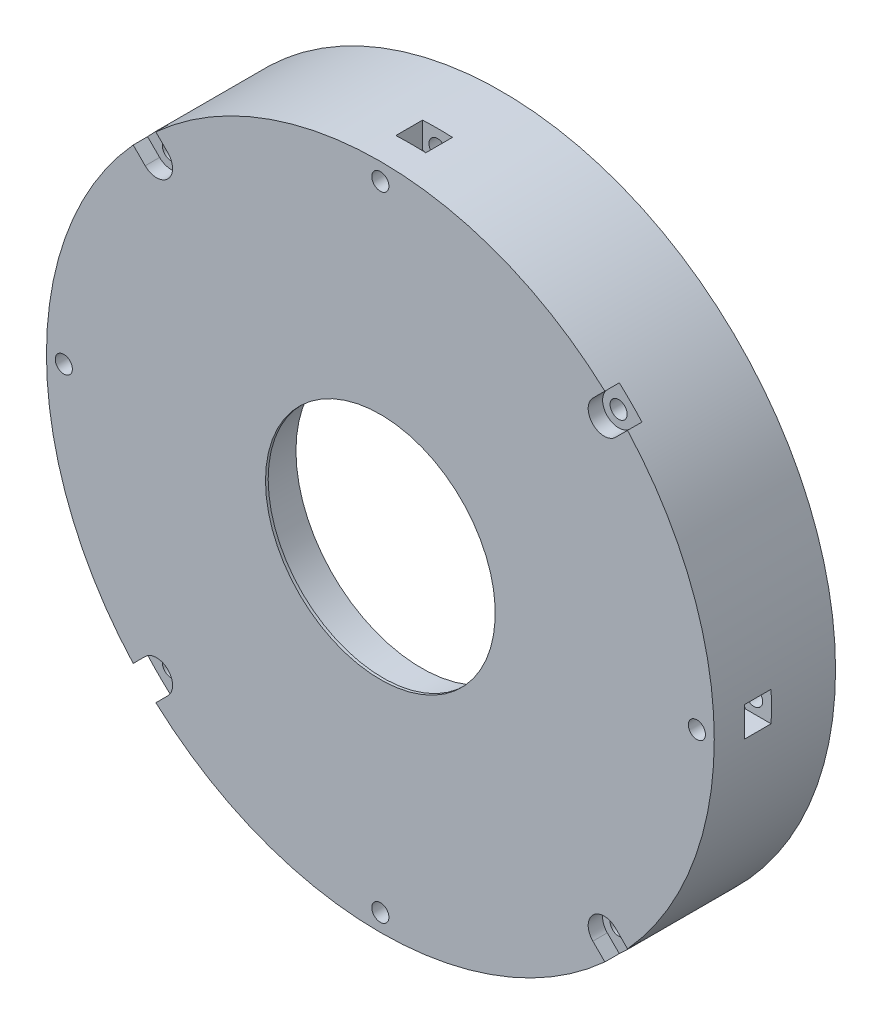
SolidWorks part; units mm, degrees
ref_plane "Front Plane" through (0, 0, 0) normal (0, 0, 1) x (1, 0, 0)
ref_plane "Top Plane" through (0, 0, 0) normal (0, 1, 0) x (1, 0, 0)
ref_plane "Right Plane" through (0, 0, 0) normal (1, 0, 0) x (0, 0, -1)
sketch "Sketch1" plane through (0, 0, 0) normal (1, 0, 0) x (0, 0, -1)
  line L0 (-8.0883, 62.5) -> (-30.7883, 62.5)
  line L1 (-30.7883, 62.5) -> (-30.7883, 21.5)
  line L2 (-30.7883, 21.5) -> (-30.2883, 21.5)
  line L3 (-30.2883, 21.5) -> (-30.2883, 23.5)
  line L4 (-30.2883, 23.5) -> (-23.0883, 23.5)
  line L5 (-8.0883, 50.75) -> (-8.0883, 62.5)
  line L6 (0, 0) -> (-105.8366, 0) construction
  line L7 (-23.0883, 23.5) -> (-23.0883, 50.75)
  line L8 (-23.0883, 50.75) -> (-8.0883, 50.75)
  line L9 (-8.0883, 52.5) -> (-30.7883, 52.5) construction
  line L12 (-26.7883, 23.5) -> (-26.7883, -23.5) construction
  line L13 (-26.7883, 23.5) -> (-26.7883, -23.5) construction
  line L14 (-26.7883, 17.5) -> (-26.7883, -17.5) construction
  line L15 (-26.7883, 17.5) -> (-26.7883, -17.5) construction
  line L16 (-23.2883, 0) -> (-30.2883, 0) construction
  line L17 (-23.2883, 0) -> (-30.2883, 0) construction
  dimension "D1" = 125
  dimension "D2" = 0.5
  dimension "D4" = 105
  dimension "D5" = 101.5
  dimension "D3" = 15
  dimension "D8" = 0.2
revolve "Revolve1" add sketch "Sketch1" angle 360 about L6
sketch "Sketch2" plane through (0, 0, 8.0883) normal (0, 0, -1) x (-1, 0, 0)
  line L3 (0, 0) -> (0, 52.5) construction
  line L4 (0, 52.5) -> (-16.8732, 46.3587)
  line L5 (-16.8732, 46.3587) -> (0, 0) construction
  circle A0 centre (0, 0) radius 52.5 construction
  circle A1 centre (0, 0) radius 54.6875 construction
  circle A2 centre (0, 0) radius 50.75 construction
  circle A3 centre (0, 0) radius 49.3339 construction
  arc A4 (0.7353, 49.3284) -> (-16.8732, 46.3587) centre (0, 0) ccw
  dimension "D1" = 105
  dimension "D2" = 101.5
  dimension "D3" = 109.375
  dimension "D4" = 20
sketch "Sketch4" plane through (0, 0, 8.0883) normal (0, 0, -1) x (-1, 0, 0)
  line L0 (0, 52.5) -> (-16.8732, 46.3587) construction
  line L1 (0, 52.5) -> (-16.8732, 46.3587)
  line L2 (-24.9846, 42.5394) -> (-1.76, 56.1799) construction
  line L3 (-32.2709, 37.3151) -> (-5.1077, 60.8064) construction
  line L4 (-38.4914, 30.8584) -> (-10.4125, 65.8827) construction
  line L5 (-43.4406, 23.3826) -> (-17.9089, 70.8158) construction
  line L6 (-46.9551, 15.1345) -> (-27.6753, 74.9503) construction
  line L7 (-8.2044, 48.6469) -> (0.6486, 50.1399) construction
  arc A0 (-16.8732, 46.3587) -> (-24.9846, 42.5394) centre (0, 0) ccw
  arc A1 (-8.2044, 48.6469) -> (-16.8732, 46.3587) centre (0, 0) ccw
  circle A2 centre (0, 0) radius 49.3339 construction
  arc A3 (-8.2044, 48.6469) -> (0.7353, 49.3284) centre (0, 0) cw
  arc A4 (0.7353, 49.3284) -> (-16.8732, 46.3587) centre (0, 0) ccw construction
  arc A5 (-24.9846, 42.5394) -> (-32.2709, 37.3151) centre (0, 0) ccw
  arc A6 (-32.2709, 37.3151) -> (-38.4914, 30.8584) centre (0, 0) ccw
  arc A7 (-38.4914, 30.8584) -> (-43.4406, 23.3826) centre (0, 0) ccw
  arc A8 (-43.4406, 23.3826) -> (-46.9551, 15.1345) centre (0, 0) ccw
  dimension "D1" = 17.9561
  dimension "D3" = 26.9341
  dimension "D4" = 35.9121
  dimension "D5" = 44.8901
  dimension "D6" = 53.8682
  dimension "D7" = 62.8462
  dimension "D9" = 8.978
  dimension "D2" = 8.978
  dimension "D8" = 8.978
sketch "Sketch5" plane through (0, 0, 8.0883) normal (0, 0, -1) x (-1, 0, 0)
  line L0 (0, 0) -> (-1.9064, 72.801) construction
  line L2 (0, 0) -> (0, 52.5) construction
  arc A0 (-1.9168, 54.6539) -> (-0.9462, 54.6793) centre (0, 0) cw
  circle A2 centre (0, 0) radius 54.6875 construction
  arc A4 (0.5323, 50.7472) -> (-3.1874, 50.6498) centre (0, 0) ccw
  circle A5 centre (0, 0) radius 50.75 construction
  spline S0 degree 3 poles (-27.6753, 74.9503) (-21.4797, 72.9452) (-13.2709, 68.8552) (-5.3211, 61.3461) (-1.9111, 56.7226) (0.0065, 52.7985) (0.676, 50.4181) (0.7353, 49.3284) knots 0 0 0 0 0.489788 0.67346 0.816315 0.918356 1 1 1 1
  spline S1 degree 3 poles (23.7148, 76.296) (17.6326, 73.9694) (9.6491, 69.4554) (2.1032, 61.5405) (-1.0602, 56.7449) (-2.7697, 52.7258) (-3.3138, 50.3136) (-3.3159, 49.2223) knots 0 0 0 0 0.489788 0.67346 0.816315 0.918356 1 1 1 1
  circle M2 centre (0, 0) radius 50.75
  dimension "D1" = 1.5
extrude "Cut-Extrude1" cut sketch "Sketch5" against normal up to surface (15 mm away) contours L0 A4 S0 A0 | L0 A0 S1 M2 region at (2.0632, 52.3141, 8.0883) region at (0.6775, 52.3504, 8.0883) up to face at (-50.75, 0, 23.0883)
pattern_circular "CirPattern1" count 60 over 360 about axis through (0, 0, 0) along (0, 0, -1) of "Cut-Extrude1" reverse direction yes
sketch "Sketch6" plane through (0, 0, 30.7883) normal (0, 0, 1) x (1, 0, 0)
  line L0 (0, 0) -> (0, 45) construction
  circle A0 centre (0, 45) radius 2.5
  circle A1 centre (45, 0) radius 2.5
  circle A2 centre (0, -45) radius 2.5
  circle A3 centre (-45, 0) radius 2.5
  point P13 (0, 0)
  dimension "D1" = 5
  dimension "D2" = 45
  dimension "D3" = 4
extrude "Cut-Extrude2" [suppressed] cut sketch "Sketch6" against normal blind 6
sketch "Sketch7" plane through (0, 0, 23.0883) normal (0, 0, -1) x (-1, 0, 0)
  circle A0 centre (0, 0) radius 27
  circle A1 centre (0, 0) radius 36
  dimension "D1" = 54
  dimension "D2" = 72
extrude "Cut-Extrude3" cut sketch "Sketch7" against normal blind 4
sketch "Sketch8" plane through (0, 0, 8.0883) normal (0, 0, -1) x (-1, 0, 0)
  line L0 (-2.8, 60.8666) -> (-2.8, 62.4372)
  line L1 (0, 56.0168) -> (2.8, 57.6334)
  line L2 (2.8, 57.6334) -> (2.8, 60.8666)
  line L3 (2.8, 60.8666) -> (0, 62.4832) construction
  line L4 (0, 62.4832) -> (-2.8, 60.8666) construction
  line L5 (-2.8, 60.8666) -> (-2.8, 57.6334)
  line L6 (-2.8, 57.6334) -> (0, 56.0168)
  line L7 (2.8, 60.8666) -> (2.8, 62.4372)
  line L8 (60.8666, 2.8) -> (62.4372, 2.8)
  line L9 (56.0168, 0) -> (57.6334, -2.8)
  line L10 (57.6334, -2.8) -> (60.8666, -2.8)
  line L11 (60.8666, 2.8) -> (57.6334, 2.8)
  line L12 (57.6334, 2.8) -> (56.0168, 0)
  line L13 (60.8666, -2.8) -> (62.4372, -2.8)
  line L14 (60.8666, -2.8) -> (62.4832, 0) construction
  line L15 (62.4832, 0) -> (60.8666, 2.8) construction
  line L16 (2.8, -60.8666) -> (2.8, -62.4372)
  line L17 (0, -56.0168) -> (-2.8, -57.6334)
  line L18 (-2.8, -57.6334) -> (-2.8, -60.8666)
  line L19 (2.8, -60.8666) -> (2.8, -57.6334)
  line L20 (2.8, -57.6334) -> (0, -56.0168)
  line L21 (-2.8, -60.8666) -> (-2.8, -62.4372)
  line L22 (-2.8, -60.8666) -> (0, -62.4832) construction
  line L23 (0, -62.4832) -> (2.8, -60.8666) construction
  line L24 (-60.8666, -2.8) -> (-62.4372, -2.8)
  line L25 (-56.0168, 0) -> (-57.6334, 2.8)
  line L26 (-57.6334, 2.8) -> (-60.8666, 2.8)
  line L27 (-60.8666, -2.8) -> (-57.6334, -2.8)
  line L28 (-57.6334, -2.8) -> (-56.0168, 0)
  line L29 (-60.8666, 2.8) -> (-62.4372, 2.8)
  line L30 (-60.8666, 2.8) -> (-62.4832, 0) construction
  line L31 (-62.4832, 0) -> (-60.8666, -2.8) construction
  line L32 (0, 59.25) -> (0, 0) construction
  line L33 (0, 0) -> (41.8961, 41.8961) construction
  line L34 (44.0174, 39.7748) -> (46.2646, 42.0219)
  line L35 (39.7748, 44.0174) -> (42.0219, 46.2646)
  line L36 (39.7748, -44.0174) -> (42.0219, -46.2646)
  line L37 (44.0174, -39.7748) -> (46.2646, -42.0219)
  line L38 (-44.0174, -39.7748) -> (-46.2646, -42.0219)
  line L39 (-39.7748, -44.0174) -> (-42.0219, -46.2646)
  line L40 (-39.7748, 44.0174) -> (-42.0219, 46.2646)
  line L41 (-44.0174, 39.7748) -> (-46.2646, 42.0219)
  line L42 (0, 59.25) -> (0, 62.5) construction
  circle A0 centre (0, 59.25) radius 1.6
  circle A1 centre (0, 59.25) radius 2.8 construction
  circle A2 centre (0, 0) radius 62.5 construction
  arc A3 (2.8, 62.4372) -> (-2.8, 62.4372) centre (0, 0) ccw
  circle A4 centre (59.25, 0) radius 1.6
  arc A5 (62.4372, -2.8) -> (62.4372, 2.8) centre (0, 0) ccw
  circle A6 centre (59.25, 0) radius 2.8 construction
  circle A7 centre (0, -59.25) radius 1.6
  arc A8 (-2.8, -62.4372) -> (2.8, -62.4372) centre (0, 0) ccw
  circle A9 centre (0, -59.25) radius 2.8 construction
  circle A10 centre (-59.25, 0) radius 1.6
  arc A11 (-62.4372, 2.8) -> (-62.4372, -2.8) centre (0, 0) ccw
  circle A12 centre (-59.25, 0) radius 2.8 construction
  arc A13 (0, 59.25) -> (41.8961, 41.8961) centre (0, 0) cw construction
  circle A14 centre (41.8961, 41.8961) radius 1.6
  arc A15 (39.7748, 44.0174) -> (44.0174, 39.7748) centre (41.8961, 41.8961) ccw
  arc A16 (42.0219, 46.2646) -> (46.2646, 42.0219) centre (0, 0) cw
  circle A17 centre (41.8961, -41.8961) radius 1.6
  arc A18 (44.0174, -39.7748) -> (39.7748, -44.0174) centre (41.8961, -41.8961) ccw
  arc A19 (46.2646, -42.0219) -> (42.0219, -46.2646) centre (0, 0) cw
  circle A20 centre (-41.8961, -41.8961) radius 1.6
  arc A21 (-39.7748, -44.0174) -> (-44.0174, -39.7748) centre (-41.8961, -41.8961) ccw
  arc A22 (-42.0219, -46.2646) -> (-46.2646, -42.0219) centre (0, 0) cw
  circle A23 centre (-41.8961, 41.8961) radius 1.6
  arc A24 (-44.0174, 39.7748) -> (-39.7748, 44.0174) centre (-41.8961, 41.8961) ccw
  arc A25 (-46.2646, 42.0219) -> (-42.0219, 46.2646) centre (0, 0) cw
  point P49 (0, 0)
  point P74 (0, 0)
  dimension "D1" = 3.2
  dimension "D3" = 5.6
  dimension "D5" = 3.2
  dimension "D6" = 6
  dimension "D7" = 45
  dimension "D8" = 4
  dimension "D2" = 3.25
  dimension "D4" = 4
extrude "Cut-Extrude4" cut sketch "Sketch8" against normal blind 5 from offset 12 contours L7 A3 L0 L5 L6 L1 L2 A0 | L29 A11 L24 L27 L28 L25 L26 A10 | L13 A5 L8 L11 L12 L9 L10 A4 | A8 L16 L19 L20 L17 L18 L21 region at (2.7143, 61.6519, 8.0883) region at (-61.6519, 2.7143, 8.0883) region at (61.6519, -2.7143, 8.0883) offset against normal yes
extrude "Cut-Extrude6" cut sketch "Sketch8<2>" against normal through all contours A10 | A0 | A4 | A7 | A20 | A23 | A14 | A17 region at (0, 59.25, 8.0883) region at (-59.25, 0, 8.0883) region at (0, -59.25, 8.0883) region at (59.25, 0, 8.0883) region at (-41.8961, 41.8961, 8.0883) region at (-41.8961, -41.8961, 8.0883) region at (41.8961, -41.8961, 8.0883) region at (41.8961, 41.8961, 8.0883)
sketch "Sketch8<2>" plane through (0, 0, 8.0883) normal (0, 0, -1) x (-1, 0, 0) same geometry as "Sketch8"
extrude "Cut-Extrude7" cut sketch "Sketch8<4>" along normal offset from surface (2.7 mm away) 20 from surface contours A25 L41 A24 L40 A23 | A16 L35 A15 L34 A14 | A19 L37 A18 L36 A17 | A22 L39 A21 L38 A20 region at (-39.8484, 39.8484, 8.0883) region at (-39.8484, -39.8484, 8.0883) region at (39.8484, -39.8484, 8.0883) region at (39.8484, 39.8484, 8.0883) up to face at (57.65, 0, 8.0883) starting at face at (57.65, 0, 30.7883)
sketch "Sketch8<4>" plane through (0, 0, 8.0883) normal (0, 0, -1) x (-1, 0, 0) same geometry as "Sketch8"
chamfer "Chamfer1" distance 2 angle 45 2 edges at (-36, 0, 27.0883) (-27, 0, 27.0883)
equation "\"D1@Sketch2\"=\"Ring Teeth Num@Drive Module.Assembly\"*\"Module@Drive Module.Assembly\""
equation "\"D2@Sketch2\"=\"D1@Sketch2\"-2*\"Addendum@Drive Module.Assembly\""
equation "\"D3@Sketch2\"=\"D1@Sketch2\"+2*\"Dedendum@Drive Module.Assembly\""
equation "\"D2@Sketch4\"=\"D8@Sketch4\""
equation "\"D3@Sketch4\"=\"D1@Sketch4\"+\"D2@Sketch4\""
equation "\"D4@Sketch4\"=\"D3@Sketch4\"+\"D2@Sketch4\""
equation "\"D5@Sketch4\"=\"D4@Sketch4\"+\"D2@Sketch4\""
equation "\"D6@Sketch4\"=\"D5@Sketch4\"+\"D2@Sketch4\""
equation "\"D7@Sketch4\"=\"D6@Sketch4\"+\"D2@Sketch4\""
equation "\"D9@Sketch4\"=\"D1@Sketch4\"-\"D8@Sketch4\""
equation "\"D1@Sketch5\"=90/\"Ring Teeth Num@Drive Module.Assembly\""
equation "\"D4@Sketch1\"=\"Ring Teeth Num@Drive Module.Assembly\"*\"Module@Drive Module.Assembly\""
equation "\"D5@Sketch1\"=\"D4@Sketch1\"-2*\"Addendum@Drive Module.Assembly\""
equation "\"D1@CirPattern1\"=\"Ring Teeth Num@Drive Module.Assembly\""
equation "\"D3@Sketch1\"=\"Gear Thickness@Drive Module.Assembly\""
